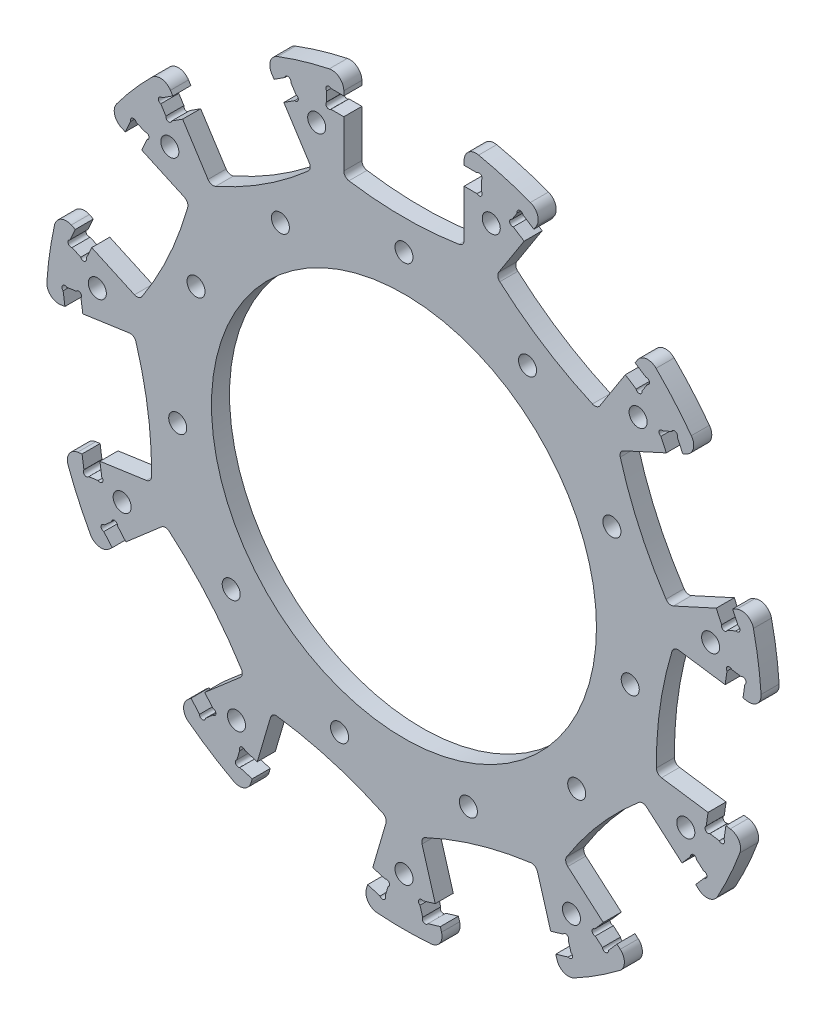
SolidWorks part; units mm, degrees
material "Thornel Mat VMA"
ref_plane "前视基准面" through (0, 0, 0) normal (0, 0, 1) x (1, 0, 0)
ref_plane "上视基准面" through (0, 0, 0) normal (0, 1, 0) x (1, 0, 0)
ref_plane "右视基准面" through (0, 0, 0) normal (1, 0, 0) x (0, 0, -1)
sketch "草图2" plane through (0, 0, 0) normal (0, 0, 1) x (1, 0, 0)
  line L0 (12.85, 52.4) -> (12.85, 55.6) construction
  line L1 (12.85, 55.6) -> (10, 55.6) construction
  line L2 (10, 52.4) -> (12.85, 52.4) construction
  line L3 (9.35, 50.9) -> (10, 50.9) construction
  line L4 (10, 50.9) -> (10, 57.1) construction
  line L5 (10, 57.1) -> (9.35, 57.1) construction
  line L6 (9.35, 46.1078) -> (9.35, 61.8922) construction
  line L7 (8.4948, 45.1184) -> (8.4948, 62.8816) construction
  line L8 (-8.4948, 62.8816) -> (-8.4948, 45.1184) construction
  line L9 (-9.35, 61.8922) -> (-9.35, 46.1078) construction
  line L10 (-10, 50.9) -> (-9.35, 50.9) construction
  line L11 (-9.35, 57.1) -> (-10, 57.1) construction
  line L12 (-10, 57.1) -> (-10, 50.9) construction
  line L13 (-10, 55.6) -> (-12.85, 55.6) construction
  line L14 (-12.85, 52.4) -> (-10, 52.4) construction
  line L15 (-12.85, 55.6) -> (-12.85, 52.4) construction
  line L16 (-8.4948, 54) -> (8.4948, 54) construction
  line L17 (10, 58.6536) -> (10, 43.8392)
  line L18 (-10, 58.6536) -> (-10, 43.8392)
  line L19 (40.1231, 43.9362) -> (32.1138, 31.4735)
  line L20 (23.298, 54.749) -> (15.2887, 42.2863)
  line L21 (57.5074, 15.2693) -> (44.0317, 9.1151)
  line L22 (49.1991, 33.4619) -> (35.7234, 27.3078)
  line L23 (56.6335, -18.2455) -> (41.9698, -16.1372)
  line L24 (59.4798, 1.5509) -> (44.8161, 3.6592)
  line L25 (37.7789, -45.9675) -> (26.5829, -36.2661)
  line L26 (50.8761, -30.8525) -> (39.6801, -21.1511)
  line L27 (6.9297, -59.0951) -> (2.756, -44.8807)
  line L28 (26.1196, -53.4604) -> (21.9459, -39.2461)
  line L29 (-26.1196, -53.4604) -> (-21.9459, -39.2461)
  line L30 (-6.9297, -59.0951) -> (-2.756, -44.8807)
  line L31 (-50.8761, -30.8525) -> (-39.6801, -21.1511)
  line L32 (-37.7789, -45.9675) -> (-26.5829, -36.2661)
  line L33 (-59.4798, 1.5509) -> (-44.8161, 3.6592)
  line L34 (-56.6335, -18.2455) -> (-41.9698, -16.1372)
  line L35 (-49.1991, 33.4619) -> (-35.7234, 27.3078)
  line L36 (-57.5074, 15.2693) -> (-44.0317, 9.1151)
  line L37 (-23.298, 54.749) -> (-15.2887, 42.2863)
  line L38 (-40.1231, 43.9362) -> (-32.1138, 31.4735)
  line L39 (0, 44.5) -> (0, 43) construction
  arc A0 (9.35, 61.8922) -> (8.4948, 62.8816) centre (8.35, 61.8922) ccw construction
  arc A1 (8.4948, 45.1184) -> (9.35, 46.1078) centre (8.35, 46.1078) ccw construction
  arc A2 (-8.4948, 45.1184) -> (8.4948, 45.1184) centre (0, 103.1567) ccw construction
  arc A3 (8.4948, 62.8816) -> (-8.4948, 62.8816) centre (0, 4.8433) ccw construction
  arc A4 (-8.4948, 62.8816) -> (-9.35, 61.8922) centre (-8.35, 61.8922) ccw construction
  arc A5 (-9.35, 46.1078) -> (-8.4948, 45.1184) centre (-8.35, 46.1078) ccw construction
  circle A6 centre (0, 0) radius 59.5 construction
  arc A7 (-10, 43.8392) -> (10, 43.8392) centre (0, 103) ccw
  arc A8 (15.2887, 42.2863) -> (32.1138, 31.4735) centre (55.686, 86.6491) ccw
  arc A9 (35.7234, 27.3078) -> (44.0317, 9.1151) centre (93.6921, 42.7877) ccw
  arc A10 (44.8161, 3.6592) -> (41.9698, -16.1372) centre (101.9516, -14.6584) ccw
  arc A11 (39.6801, -21.1511) -> (26.5829, -36.2661) centre (77.8422, -67.4507) ccw
  arc A12 (21.9459, -39.2461) -> (2.756, -44.8807) centre (29.0185, -98.8278) ccw
  arc A13 (-2.756, -44.8807) -> (-21.9459, -39.2461) centre (-29.0185, -98.8278) ccw
  arc A14 (-26.5829, -36.2661) -> (-39.6801, -21.1511) centre (-77.8422, -67.4507) ccw
  arc A15 (-41.9698, -16.1372) -> (-44.8161, 3.6592) centre (-101.9516, -14.6584) ccw
  arc A16 (-44.0317, 9.1151) -> (-35.7234, 27.3078) centre (-93.6921, 42.7877) ccw
  arc A17 (-32.1138, 31.4735) -> (-15.2887, 42.2863) centre (-55.686, 86.6491) ccw
  arc A18 (-23.298, 54.749) -> (-10, 58.6536) centre (0, 0) cw
  arc A19 (10, 58.6536) -> (23.298, 54.749) centre (0, 0) cw
  arc A20 (40.1231, 43.9362) -> (49.1991, 33.4619) centre (0, 0) cw
  arc A21 (57.5074, 15.2693) -> (59.4798, 1.5509) centre (0, 0) cw
  arc A22 (56.6335, -18.2455) -> (50.8761, -30.8525) centre (0, 0) cw
  arc A23 (37.7789, -45.9675) -> (26.1196, -53.4604) centre (0, 0) cw
  arc A24 (6.9297, -59.0951) -> (-6.9297, -59.0951) centre (0, 0) cw
  arc A25 (-49.1991, 33.4619) -> (-40.1231, 43.9362) centre (0, 0) cw
  arc A26 (-57.5074, 15.2693) -> (-59.4798, 1.5509) centre (0, 0) ccw
  arc A27 (-56.6335, -18.2455) -> (-50.8761, -30.8525) centre (0, 0) ccw
  arc A28 (-37.7789, -45.9675) -> (-26.1196, -53.4604) centre (0, 0) ccw
  circle A29 centre (0, 0) radius 63.5 construction
  circle A30 centre (0, 0) radius 32
  circle A31 centre (0, -51.5) radius 1.5
  circle A32 centre (-27.843, -43.3246) radius 1.5
  circle A33 centre (-46.846, -21.3939) radius 1.5
  circle A34 centre (-50.9758, 7.3292) radius 1.5
  circle A35 centre (-38.9211, 33.7253) radius 1.5
  circle A36 centre (-14.5092, 49.4139) radius 1.5
  circle A37 centre (14.5092, 49.4139) radius 1.5
  circle A38 centre (38.9211, 33.7253) radius 1.5
  circle A39 centre (50.9758, 7.3292) radius 1.5
  circle A40 centre (46.846, -21.3939) radius 1.5
  circle A41 centre (27.843, -43.3246) radius 1.5
  circle A42 centre (0, 38) radius 1.5
  circle A43 centre (20.5444, 31.9676) radius 1.5
  circle A44 centre (34.566, 15.7858) radius 1.5
  circle A45 centre (37.6132, -5.408) radius 1.5
  circle A46 centre (28.7185, -24.8847) radius 1.5
  circle A47 centre (10.7058, -36.4607) radius 1.5
  circle A48 centre (-10.7058, -36.4607) radius 1.5
  circle A49 centre (-28.7185, -24.8847) radius 1.5
  circle A50 centre (-37.6132, -5.408) radius 1.5
  circle A51 centre (-34.566, 15.7858) radius 1.5
  circle A52 centre (-20.5444, 31.9676) radius 1.5
  point P37 (-12.85, 54)
  point P41 (-9.675, 57.1)
  point P42 (-9.675, 50.9)
  point P43 (0, 63.5)
  point P44 (0, 44.5)
  point P45 (-10, 54)
  point P46 (-9.35, 54)
  point P47 (9.35, 54)
  point P48 (10, 54)
  point P49 (12.85, 54)
  point P54 (0, 54)
  point P108 (0, 0)
  point P132 (0, 0)
  point P155 (0, 0)
  dimension "D1" = 25.7
  dimension "D8" = 1
  dimension "D9" = 58.6567
  dimension "D11" = 119
  dimension "D12" = 60
  dimension "D15" = 127
  dimension "D16" = 64
  dimension "D17" = 3
  dimension "D20" = 3
  dimension "D2" = 3.2
  dimension "D3" = 6.2
  dimension "D4" = 20
  dimension "D5" = 19
  dimension "D6" = 18.7
  dimension "D7" = 54
  dimension "D10" = 16.9896
  dimension "D13" = 1.5
  dimension "D18" = 51.5
  dimension "D21" = 38
  dimension "D14" = 11
  dimension "D19" = 11
  dimension "D22" = 11
extrude "凸台-拉伸1" add sketch "草图2" along normal mid plane 3
fillet "圆角1" radius 1 22 edges at (10, 43.8392, 0) (-10, 43.8392, 0) (-15.2887, 42.2863, 0) (-32.1138, 31.4735, 0) (-35.7234, 27.3078, 0) (-44.0317, 9.1151, 0) (-44.8161, 3.6592, 0) (-41.9698, -16.1372, 0) (-39.6801, -21.1511, 0) (-26.5829, -36.2661, 0) (-21.9459, -39.2461, 0) (-2.756, -44.8807, 0) (2.756, -44.8807, 0) (21.9459, -39.2461, 0) (26.5829, -36.2661, 0) (39.6801, -21.1511, 0) (41.9698, -16.1372, 0) (44.8161, 3.6592, 0) (44.0317, 9.1151, 0) (35.7234, 27.3078, 0) (32.1138, 31.4735, 0) (15.2887, 42.2863, 0)
fillet "圆角2" radius 2 22 edges at (10, 58.6536, 0) (-10, 58.6536, 0) (-23.298, 54.749, 0) (-40.1231, 43.9362, 0) (-49.1991, 33.4619, 0) (-57.5074, 15.2693, 0) (-59.4798, 1.5509, 0) (-56.6335, -18.2455, 0) (-50.8761, -30.8525, 0) (-37.7789, -45.9675, 0) (-26.1196, -53.4604, 0) (-6.9297, -59.0951, 0) (6.9297, -59.0951, 0) (26.1196, -53.4604, 0) (37.7789, -45.9675, 0) (50.8761, -30.8525, 0) (56.6335, -18.2455, 0) (59.4798, 1.5509, 0) (57.5074, 15.2693, 0) (49.1991, 33.4619, 0) (40.1231, 43.9362, 0) (23.298, 54.749, 0)
ref_axis "基准轴1" through (0, 0, 1.5) along (0, 0, -1)
sketch "草图3" plane through (0, 0, 1.5) normal (0, 0, 1) x (1, 0, 0)
  line L0 (-10, 54) -> (10, 54) construction
  line L1 (-10, 52.5) -> (-12.85, 52.5)
  line L2 (-10, 44.6905) -> (-10, 56.2339) construction
  line L3 (-12.85, 52.5) -> (-12.85, 55.5)
  line L4 (-12.85, 55.5) -> (-10, 55.5)
  line L5 (-10, 55.5) -> (-10, 52.5)
  line L6 (10, 55.5) -> (12.85, 55.5)
  line L7 (10, 56.2339) -> (10, 44.6905) construction
  line L8 (12.85, 55.5) -> (12.85, 52.5)
  line L9 (12.85, 52.5) -> (10, 52.5)
  line L10 (10, 52.5) -> (10, 55.5)
  line L11 (19.9711, 49.5722) -> (17.5735, 51.113)
  line L12 (17.5735, 51.113) -> (19.1955, 53.6368)
  line L13 (19.1955, 53.6368) -> (21.593, 52.096)
  line L14 (38.4181, 41.2832) -> (40.8157, 39.7423)
  line L15 (40.8157, 39.7423) -> (39.1938, 37.2186)
  line L16 (39.1938, 37.2186) -> (36.7962, 38.7594)
  line L17 (36.7962, 38.7594) -> (38.4181, 41.2832)
  line L18 (21.593, 52.096) -> (19.9711, 49.5722)
  line L19 (43.6015, 30.9056) -> (42.4176, 33.4981)
  line L20 (42.4176, 33.4981) -> (45.1465, 34.7443)
  line L21 (45.1465, 34.7443) -> (46.3304, 32.1519)
  line L22 (54.6387, 13.9592) -> (55.8227, 11.3668)
  line L23 (55.8227, 11.3668) -> (53.0938, 10.1205)
  line L24 (53.0938, 10.1205) -> (51.9098, 12.713)
  line L25 (51.9098, 12.713) -> (54.6387, 13.9592)
  line L26 (46.3304, 32.1519) -> (43.6015, 30.9056)
  line L27 (53.3888, 2.4267) -> (53.7944, 5.2477)
  line L28 (53.7944, 5.2477) -> (56.7638, 4.8207)
  line L29 (56.7638, 4.8207) -> (56.3582, 1.9997)
  line L30 (53.5119, -17.7967) -> (53.1063, -20.6177)
  line L31 (53.1063, -20.6177) -> (50.1369, -20.1907)
  line L32 (50.1369, -20.1907) -> (50.5425, -17.3697)
  line L33 (50.5425, -17.3697) -> (53.5119, -17.7967)
  line L34 (56.3582, 1.9997) -> (53.3888, 2.4267)
  line L35 (46.2255, -26.8227) -> (48.0918, -24.6688)
  line L36 (48.0918, -24.6688) -> (50.3591, -26.6334)
  line L37 (50.3591, -26.6334) -> (48.4927, -28.7873)
  line L38 (35.3955, -43.9023) -> (33.5291, -46.0562)
  line L39 (33.5291, -46.0562) -> (31.2619, -44.0916)
  line L40 (31.2619, -44.0916) -> (33.1282, -41.9377)
  line L41 (33.1282, -41.9377) -> (35.3955, -43.9023)
  line L42 (48.4927, -28.7873) -> (46.2255, -26.8227)
  line L43 (24.3859, -47.5561) -> (27.1204, -46.7531)
  line L44 (27.1204, -46.7531) -> (27.9656, -49.6316)
  line L45 (27.9656, -49.6316) -> (25.2311, -50.4345)
  line L46 (6.0412, -56.0692) -> (3.3067, -56.8721)
  line L47 (3.3067, -56.8721) -> (2.4615, -53.9936)
  line L48 (2.4615, -53.9936) -> (5.196, -53.1907)
  line L49 (5.196, -53.1907) -> (6.0412, -56.0692)
  line L50 (25.2311, -50.4345) -> (24.3859, -47.5561)
  line L51 (-5.196, -53.1907) -> (-2.4615, -53.9936)
  line L52 (-2.4615, -53.9936) -> (-3.3067, -56.8721)
  line L53 (-3.3067, -56.8721) -> (-6.0412, -56.0692)
  line L54 (-25.2311, -50.4345) -> (-27.9656, -49.6316)
  line L55 (-27.9656, -49.6316) -> (-27.1204, -46.7531)
  line L56 (-27.1204, -46.7531) -> (-24.3859, -47.5561)
  line L57 (-24.3859, -47.5561) -> (-25.2311, -50.4345)
  line L58 (-6.0412, -56.0692) -> (-5.196, -53.1907)
  line L59 (-33.1282, -41.9377) -> (-31.2619, -44.0916)
  line L60 (-31.2619, -44.0916) -> (-33.5291, -46.0562)
  line L61 (-33.5291, -46.0562) -> (-35.3955, -43.9023)
  line L62 (-48.4927, -28.7873) -> (-50.3591, -26.6334)
  line L63 (-50.3591, -26.6334) -> (-48.0918, -24.6688)
  line L64 (-48.0918, -24.6688) -> (-46.2255, -26.8227)
  line L65 (-46.2255, -26.8227) -> (-48.4927, -28.7873)
  line L66 (-35.3955, -43.9023) -> (-33.1282, -41.9377)
  line L67 (-50.5425, -17.3697) -> (-50.1369, -20.1907)
  line L68 (-50.1369, -20.1907) -> (-53.1063, -20.6177)
  line L69 (-53.1063, -20.6177) -> (-53.5119, -17.7967)
  line L70 (-56.3582, 1.9997) -> (-56.7638, 4.8207)
  line L71 (-56.7638, 4.8207) -> (-53.7944, 5.2477)
  line L72 (-53.7944, 5.2477) -> (-53.3888, 2.4267)
  line L73 (-53.3888, 2.4267) -> (-56.3582, 1.9997)
  line L74 (-53.5119, -17.7967) -> (-50.5425, -17.3697)
  line L75 (-51.9098, 12.713) -> (-53.0938, 10.1205)
  line L76 (-53.0938, 10.1205) -> (-55.8227, 11.3668)
  line L77 (-55.8227, 11.3668) -> (-54.6387, 13.9592)
  line L78 (-46.3304, 32.1519) -> (-45.1465, 34.7443)
  line L79 (-45.1465, 34.7443) -> (-42.4176, 33.4981)
  line L80 (-42.4176, 33.4981) -> (-43.6015, 30.9056)
  line L81 (-43.6015, 30.9056) -> (-46.3304, 32.1519)
  line L82 (-54.6387, 13.9592) -> (-51.9098, 12.713)
  line L83 (-36.7962, 38.7594) -> (-39.1938, 37.2186)
  line L84 (-39.1938, 37.2186) -> (-40.8157, 39.7423)
  line L85 (-40.8157, 39.7423) -> (-38.4181, 41.2832)
  line L86 (-21.593, 52.096) -> (-19.1955, 53.6368)
  line L87 (-19.1955, 53.6368) -> (-17.5735, 51.113)
  line L88 (-17.5735, 51.113) -> (-19.9711, 49.5722)
  line L89 (-19.9711, 49.5722) -> (-21.593, 52.096)
  line L90 (-38.4181, 41.2832) -> (-36.7962, 38.7594)
  point P2 (0, 54)
  point P17 (-10, 54)
  point P18 (10, 54)
  point P100 (0, 0)
  dimension "D1" = 54
  dimension "D2" = 20
  dimension "D3" = 3
  dimension "D4" = 25.7
  dimension "D5" = 11
extrude "切除-拉伸1" cut sketch "草图3" against normal through all
sketch "草图4" plane through (0, 0, 1.5) normal (0, 0, 1) x (1, 0, 0)
  line L0 (-12.85, 55.5) -> (-11.35, 54) construction
  line L1 (-11.35, 54) -> (-12.85, 52.5) construction
  line L2 (-12.85, 55.5) -> (-12.85, 52.5) construction
  line L3 (-12.85, 52.5) -> (-10, 52.5) construction
  line L4 (12.85, 55.5) -> (11.35, 54) construction
  line L5 (11.35, 54) -> (12.85, 52.5) construction
  line L6 (-10, 55.5) -> (-12.85, 55.5) construction
  line L7 (12.85, 55.5) -> (10, 55.5) construction
  line L9 (10, 52.5) -> (12.85, 52.5) construction
  circle A0 centre (12.4964, 55.1464) radius 0.5
  circle A1 centre (12.4964, 52.8536) radius 0.5
  circle A2 centre (-12.4964, 55.1464) radius 0.5
  circle A3 centre (-12.4964, 52.8536) radius 0.5
  circle A4 centre (19.3017, 53.1482) radius 0.5
  circle A5 centre (18.0621, 51.2193) radius 0.5
  circle A6 centre (40.3271, 39.6361) radius 0.5
  circle A7 centre (39.0875, 37.7071) radius 0.5
  circle A8 centre (44.9718, 34.2758) radius 0.5
  circle A9 centre (42.8861, 33.3233) radius 0.5
  circle A10 centre (55.3542, 11.5415) radius 0.5
  circle A11 centre (53.2685, 10.589) radius 0.5
  circle A12 centre (56.3636, 4.5211) radius 0.5
  circle A13 centre (54.094, 4.8474) radius 0.5
  circle A14 centre (52.8067, -20.2174) radius 0.5
  circle A15 centre (50.5372, -19.8911) radius 0.5
  circle A16 centre (49.8603, -26.6691) radius 0.5
  circle A17 centre (48.1275, -25.1675) radius 0.5
  circle A18 centre (33.4935, -45.5574) radius 0.5
  circle A19 centre (31.7606, -44.0559) radius 0.5
  circle A20 centre (27.5268, -49.392) radius 0.5
  circle A21 centre (26.8808, -47.192) radius 0.5
  circle A22 centre (3.5463, -56.4333) radius 0.5
  circle A23 centre (2.9003, -54.2333) radius 0.5
  circle A24 centre (-3.5463, -56.4333) radius 0.5
  circle A25 centre (-2.9003, -54.2333) radius 0.5
  circle A26 centre (-27.5268, -49.392) radius 0.5
  circle A27 centre (-26.8808, -47.192) radius 0.5
  circle A28 centre (-33.4935, -45.5574) radius 0.5
  circle A29 centre (-31.7606, -44.0559) radius 0.5
  circle A30 centre (-49.8603, -26.6691) radius 0.5
  circle A31 centre (-48.1275, -25.1675) radius 0.5
  circle A32 centre (-52.8067, -20.2174) radius 0.5
  circle A33 centre (-50.5372, -19.8911) radius 0.5
  circle A34 centre (-56.3636, 4.5211) radius 0.5
  circle A35 centre (-54.094, 4.8474) radius 0.5
  circle A36 centre (-55.3542, 11.5415) radius 0.5
  circle A37 centre (-53.2685, 10.589) radius 0.5
  circle A38 centre (-44.9718, 34.2758) radius 0.5
  circle A39 centre (-42.8861, 33.3233) radius 0.5
  circle A40 centre (-40.3271, 39.6361) radius 0.5
  circle A41 centre (-39.0875, 37.7071) radius 0.5
  circle A42 centre (-19.3017, 53.1482) radius 0.5
  circle A43 centre (-18.0621, 51.2193) radius 0.5
  point P110 (0, 0)
  dimension "D5" = 1
  dimension "D1" = 45
  dimension "D2" = 45
  dimension "D3" = 45
  dimension "D4" = 45
  dimension "D6" = 11
extrude "切除-拉伸2" cut sketch "草图4" against normal through all
